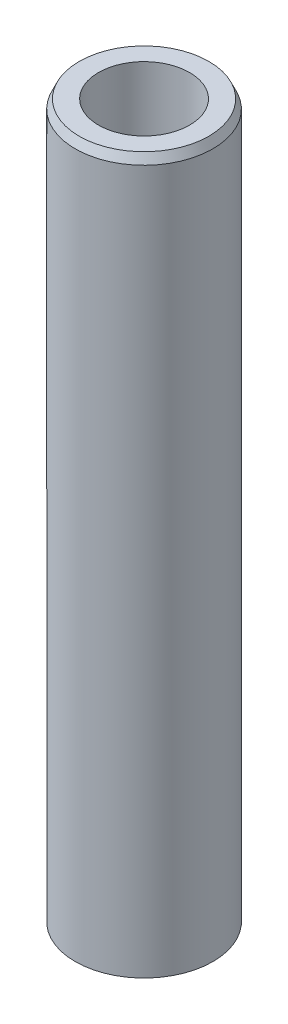
SolidWorks part; units mm, degrees
ref_plane "Front Plane" through (0, 0, 0) normal (0, 0, 1) x (1, 0, 0)
ref_plane "Top Plane" through (0, 0, 0) normal (0, 1, 0) x (1, 0, 0)
ref_plane "Right Plane" through (0, 0, 0) normal (1, 0, 0) x (0, 0, -1)
sketch "Sketch1" plane through (0, 0, 0) normal (0, 1, 0) x (1, 0, 0)
  circle A0 centre (0, 0) radius 30
  dimension "SHAFT_OD" = 60
extrude "Boss-Extrude1" add sketch "Sketch1" along normal blind 312.2951
sketch "Sketch2" plane through (0, 0, 0) normal (0, 1, 0) x (1, 0, 0)
  circle A0 centre (0, 0) radius 19.8548
  dimension "BORE_D" = 39.7097
extrude "Cut-Extrude1" cut sketch "Sketch2" along normal through all
chamfer "Chamfer1" distance 3.8672 angle 24.533 2 edges at (0, 312.2951, 30) (0, 0, 30) first distance on face at (0, 312.2951, 30) first distance on face at (0, 0, 19.8548)
